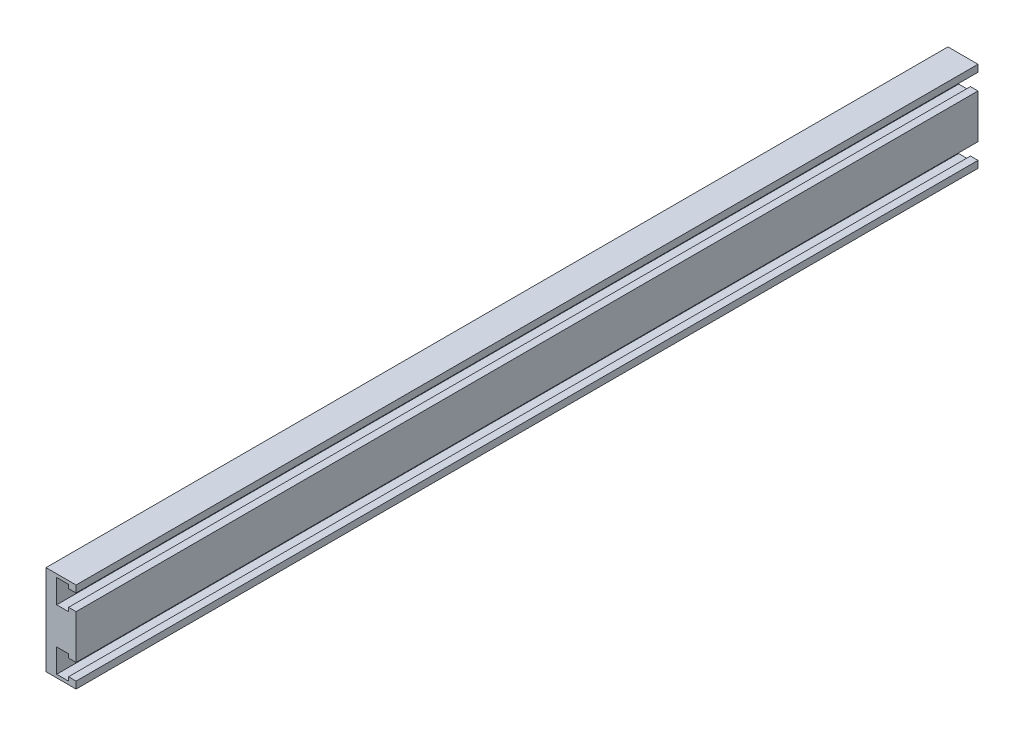
SolidWorks part; units mm, degrees
ref_plane "Front Plane" through (0, 0, 0) normal (0, 0, 1) x (1, 0, 0)
ref_plane "Top Plane" through (0, 0, 0) normal (0, 1, 0) x (1, 0, 0)
ref_plane "Right Plane" through (0, 0, 0) normal (1, 0, 0) x (0, 0, -1)
sketch "Sketch1" plane through (0, 0, 0) normal (0, 0, 1) x (1, 0, 0)
  line L2 (-6.35, -19.05) -> (-6.35, 19.05)
  line L3 (-6.35, 19.05) -> (6.35, 19.05)
  line L5 (6.35, 16.1125) -> (3.175, 16.1125)
  line L6 (3.175, 16.1125) -> (3.175, 17.7)
  line L14 (6.35, 16.1125) -> (6.35, 19.05)
  line L22 (3.175, 17.7) -> (-1.825, 17.7)
  line L23 (-1.825, 17.7) -> (-1.825, 7.7)
  line L24 (-1.825, 7.7) -> (3.175, 7.7)
  line L25 (3.175, 7.7) -> (3.175, 9.2875)
  line L26 (3.175, 9.2875) -> (6.35, 9.2875)
  line L28 (6.35, 9.2875) -> (6.35, -9.2875)
  line L29 (0, 0) -> (33.7899, 0) construction
  line L30 (3.175, -9.2875) -> (6.35, -9.2875)
  line L31 (3.175, -7.7) -> (3.175, -9.2875)
  line L32 (-1.825, -7.7) -> (3.175, -7.7)
  line L33 (-1.825, -17.7) -> (-1.825, -7.7)
  line L34 (3.175, -17.7) -> (-1.825, -17.7)
  line L35 (6.35, -16.1125) -> (6.35, -19.05)
  line L36 (3.175, -16.1125) -> (3.175, -17.7)
  line L37 (6.35, -16.1125) -> (3.175, -16.1125)
  line L38 (-6.35, -19.05) -> (6.35, -19.05)
  line L39 (0.675, 17.7) -> (0.675, 7.7) construction
  line L40 (0.675, -7.7) -> (0.675, -17.7) construction
  point P0 (0, 0)
  point P4 (6.35, 0)
  point P26 (-6.35, 0)
  point P30 (0.675, -12.7)
  point P31 (0.675, 12.7)
  dimension "D2" = 25.4
  dimension "D3" = 1.5875
  dimension "D4" = 1.5875
  dimension "D7" = 10
  dimension "D12" = 12.7
  dimension "D15" = 5
  dimension "D16" = 4.525
extrude "Boss-Extrude1" add sketch "Sketch1" along normal blind 190.5 and the other way blind 190.5 contours L2 L3 L14 L5 L6 L22 L23 L24 L25 L26 L28 L30 L31 L32 L33 L34 L36 L37 L35 L38
